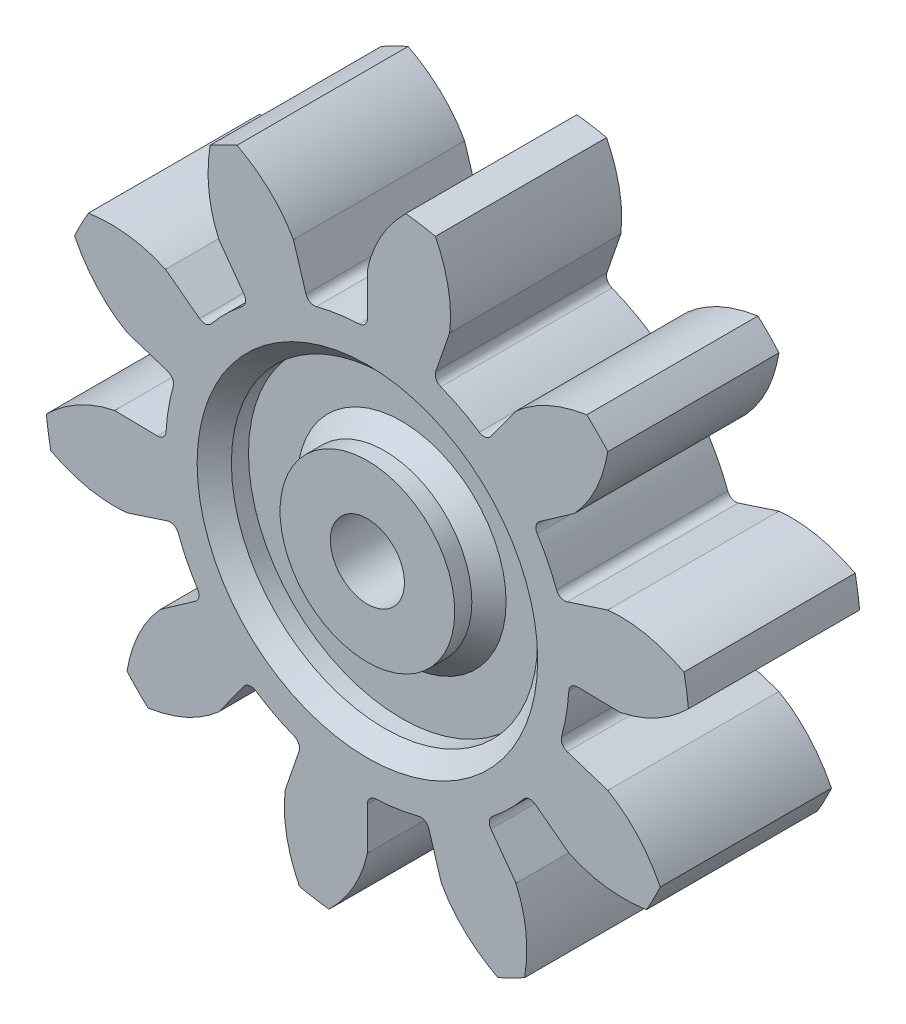
SolidWorks part; units mm, degrees
ref_plane "Front Plane" through (0, 0, 0) normal (0, 0, 1) x (1, 0, 0)
ref_plane "Top Plane" through (0, 0, 0) normal (0, 1, 0) x (1, 0, 0)
ref_plane "Right Plane" through (0, 0, 0) normal (1, 0, 0) x (0, 0, -1)
sketch "Sketch1" plane through (0, 0, 0) normal (0, 0, 1) x (1, 0, 0)
  circle A0 centre (0, 0) radius 18.852
  circle A1 centre (0, 0) radius 15.71
  circle A2 centre (0, 0) radius 14.7626
  circle A3 centre (0, 0) radius 12.568
  circle A4 centre (0, 0) radius 11.7825
  dimension "Root" = 23.565
  dimension "Clearance" = 25.136
  dimension "Base" = 29.5251
  dimension "Pitch" = 31.42
  dimension "Addenum" = 37.704
sketch "Sketch2" plane through (0, 0, 0) normal (0, 0, 1) x (1, 0, 0)
  line L0 (0, 0) -> (0, 14.7626)
  line L1 (0, 0) -> (7.3813, 12.7848) construction
  line L2 (0, 0) -> (12.7848, 7.3813) construction
  line L3 (0, 0) -> (14.7626, 0) construction
  line L4 (14.7626, 0) -> (14.7626, 23.189) construction
  line L5 (12.7848, 7.3813) -> (5.0551, 20.7695) construction
  line L6 (7.3813, 12.7848) -> (0.6872, 16.6496) construction
  line L7 (0, 0) -> (4.8547, 14.9411) construction
  line L8 (0, 0) -> (9.2341, 12.7097)
  line L9 (2.5912, 15.4948) -> (0, 0) construction
  line L10 (4.8031, 13.9594) -> (0, 0)
  circle A2 centre (0, 0) radius 14.7626 construction
  arc A3 (4.5619, 14.04) -> (0, 14.7626) centre (0, 0) ccw
  circle A4 centre (0, 0) radius 15.71 construction
  arc A5 (4.8547, 14.9411) -> (0.2706, 15.7077) centre (0, 0) ccw
  spline S0 degree 3 poles (0, 14.7626) (1.2986, 20.8081) (9.7808, 23.1969) (14.7626, 23.189) knots 0 0 0 0 1 1 1 1
  spline S1 degree 3 poles (4.8031, 13.9594) (5.5421, 20.0984) (-1.7015, 25.117) (-6.4147, 26.7304) knots 0 0 0 0 1 1 1 1
  point P10 (0, 0)
  dimension "D2" = 90
  dimension "D3" = 23.189
  dimension "D4" = 15.4593
  dimension "D5" = 7.7297
  dimension "Circulare pitch" = 36
  dimension "D1" = 4
sketch "Sketch3" plane through (0, 0, 0) normal (0, 0, 1) x (1, 0, 0)
  line L0 (4.8031, 13.9594) -> (0, 0) construction
  line L1 (0, 0) -> (0, 14.7626) construction
  line L2 (4.8031, 13.9594) -> (3.8335, 11.1414)
  line L3 (0, 11.7825) -> (0, 14.7626)
  circle A0 centre (0, 0) radius 11.7825 construction
  circle A1 centre (0, 0) radius 18.852 construction
  arc A2 (3.8335, 11.1414) -> (0, 11.7825) centre (0, 0) ccw
  arc A3 (3.9709, 18.429) -> (2.2411, 18.7183) centre (0, 0) ccw
  spline S0 degree 3 poles (3883.1383, -925.1744) (-4080.4899, 636.3662) (4139.6336, -300.8674) (-3982.4642, 99.0781) knots -6.53892 -6.53892 -6.53892 -6.53892 7.954263 7.954263 7.954263 7.954263 only from (0, 14.7626) to (14.7626, 23.189) construction
  spline S1 degree 3 poles (-3972.8744, 388.5608) (4065.5234, -725.8649) (-4012.293, 1062.3525) (3798.0217, -1202.027) knots -6.53892 -6.53892 -6.53892 -6.53892 7.954263 7.954263 7.954263 7.954263 only from (4.8031, 13.9594) to (-6.4147, 26.7304) construction
  spline S2 degree 3 poles (0, 14.7626) (0.3335, 16.3152) (1.1409, 17.6267) (2.2411, 18.7183) knots 0 0 0 0 0.256831 0.256831 0.256831 0.256831
  spline S3 degree 3 poles (4.8031, 13.9594) (4.9929, 15.5361) (4.6561, 17.0389) (3.9709, 18.429) knots 0 0 0 0 0.256831 0.256831 0.256831 0.256831
extrude "Boss-Extrude1" add sketch "Sketch3" along normal blind 10
ref_axis "Axis1" through (0, 0, 0) along (0, 0, 1)
pattern_circular "CirPattern1" count 10 over 360 about axis through (0, 0, 0) along (0, 0, 1) of bodies 101
extrude "Boss-Extrude2" add sketch "Sketch1" along normal blind 10 contours A4 region at (0, 0, 0)
sketch "Sketch4" plane through (0, 0, 10) normal (0, 0, 1) x (1, 0, 0)
  circle A0 centre (0, 0) radius 8.9461
  circle A1 centre (0, 0) radius 5.1013
  circle A2 centre (0, 0) radius 2.1636
extrude "Cut-Extrude1" cut sketch "Sketch4" against normal blind 2 contours A0 A1 region at (-8.693, 0, 10)
extrude "Cut-Extrude2" cut sketch "Sketch4<3>" against normal through all contours A2 region at (0, 0, 10)
sketch "Sketch4<3>" plane through (0, 0, 10) normal (0, 0, 1) x (1, 0, 0) same geometry as "Sketch4"
sketch "Sketch5" plane through (0, 0, 0) normal (0, 0, -1) x (-1, 0, 0)
  circle A1 centre (0, 0) radius 2.1636
  circle A2 centre (0, 0) radius 2.1636
  circle A3 centre (0, 0) radius 5.1013
  circle A4 centre (0, 0) radius 5.1013
  circle A5 centre (0, 0) radius 8.9461
  circle A6 centre (0, 0) radius 8.9461
  dimension "D1" = 0
  dimension "D2" = 0
  dimension "D3" = 0
extrude "Cut-Extrude3" cut sketch "Sketch5" against normal blind 2 contours A6 A4 region at (8.693, 0, 0)
fillet "Fillet1" radius 0.5 20 edges at (-3.4474, 11.2669, 5) (-11.2058, 3.641, 5) (-6.9256, 9.5322, 5) (-9.6501, -6.7603, 5) (-11.7808, 0.203, 5) (-9.4115, 7.0888, 5) (0, 11.7825, 5) (6.9256, 9.5322, 5) (-3.8335, -11.1414, 5) (-11.2058, -3.641, 5) (-6.9256, -9.5322, 5) (0, -11.7825, 5) (3.4474, -11.2669, 5) (9.4115, -7.0888, 5) (3.8335, 11.1414, 5) (6.9256, -9.5322, 5) (11.2058, -3.641, 5) (11.7808, -0.203, 5) (11.2058, 3.641, 5) (9.6501, 6.7603, 5)
chamfer "Chamfer1" distance 1 angle 45 2 edges at (5.1013, 0, 8) (-5.1013, 0, 2)
chamfer "Chamfer2" distance 1 angle 45 2 edges at (8.9461, 0, 10) (-8.9461, 0, 0)
equation "\"Module\"= 3.142"
equation "\"No of teeth\"= 10"
equation "\"Pressure angle\" = 20deg"
equation "\"Pitch@Sketch1\"= \"Module\" * \"No of teeth\""
equation "\"Addenum@Sketch1\" = \"Pitch@Sketch1\" + ( \"Module\" * 2 )"
equation "\"Clearance@Sketch1\"= \"Pitch@Sketch1\" - ( \"Module\" * 2 )"
equation "\"Root@Sketch1\"= \"Pitch@Sketch1\" - ( ( \"Module\" * 1.25 ) * 2 )"
equation "\"Base@Sketch1\"= \"Pitch@Sketch1\" * cos ( \"Pressure angle\" )"
equation "\"D3@Sketch2\"= \"Base@Sketch1\" * pi / 4"
equation "\"D4@Sketch2\"=\"D3@Sketch2\"/3*2"
equation "\"D5@Sketch2\"=\"D3@Sketch2\"/3"
equation "\"Circulare pitch@Sketch2\"= 360 / \"No of teeth\""
equation "\"D1@CirPattern1\"=\"No of teeth\""
